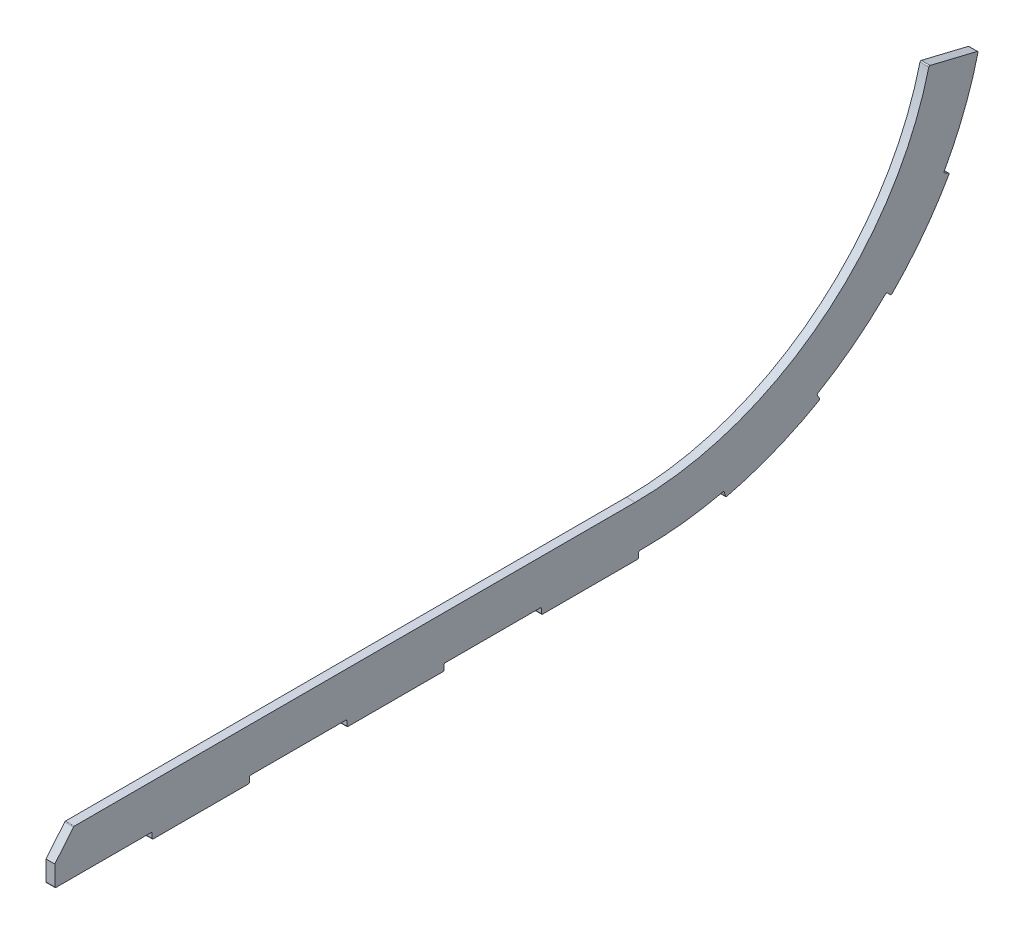
SolidWorks part; units mm, degrees
material "MS-Grade 400"
ref_plane "Front Plane" through (0, 0, 0) normal (0, 0, 1) x (1, 0, 0)
ref_plane "Top Plane" through (0, 0, 0) normal (0, 1, 0) x (1, 0, 0)
ref_plane "Right Plane" through (0, 0, 0) normal (1, 0, 0) x (0, 0, -1)
sketch "Sketch1" plane through (0, 0, 0) normal (1, 0, 0) x (0, 0, -1)
  line L0 (531, -15) -> (442.5, -15)
  line L1 (535.8793, -9) -> (531, -9)
  line L2 (0, 10) -> (17.3111, 31)
  line L3 (88.5, -9) -> (88.5, -15)
  line L4 (527.7481, 31) -> (17.3111, 31)
  line L5 (177, -9) -> (177, -15)
  line L6 (265.5, -9) -> (265.5, -15)
  line L7 (354, -9) -> (354, -15)
  line L8 (442.5, -9) -> (442.5, -15)
  line L9 (527.7481, 306) -> (610.0536, -6.2428) construction
  line L10 (535.8793, 303.5117) -> (695.9383, 28.1378) construction
  line L11 (527.7481, 306) -> (813.5032, 147.3879) construction
  line L12 (527.7481, 306) -> (760.5602, 77.7504) construction
  line L13 (535.8793, 303.5117) -> (535.8793, -9) construction
  line L14 (527.7481, 306) -> (839.704, 230.3395) construction
  line L15 (795, 241.1818) -> (839.704, 230.3395)
  line L16 (535.8793, -15) -> (0, -15) construction
  line L17 (88.5, -9) -> (0, -9)
  line L19 (0, 10) -> (0, -9)
  line L20 (535.8793, -9) -> (0, -9) construction
  line L21 (177, -15) -> (88.5, -15)
  line L22 (265.5, -9) -> (177, -9)
  line L23 (354, -15) -> (265.5, -15)
  line L24 (610.0536, -6.2428) -> (608.5239, -0.4395)
  line L25 (695.9383, 28.1378) -> (692.9232, 33.3251)
  line L26 (760.5602, 77.7504) -> (756.2755, 81.9511)
  line L27 (813.5032, 147.3879) -> (808.2572, 150.2998)
  line L28 (531, -9) -> (531, -15)
  line L29 (442.5, -9) -> (354, -9)
  arc A0 (535.8793, -9) -> (608.5239, -0.4395) centre (535.8793, 303.5117) ccw
  arc A2 (535.8793, -9) -> (839.0432, 227.6483) centre (535.8793, 303.5117) ccw construction
  arc A3 (535.8793, -15) -> (844.8637, 226.1917) centre (535.8793, 303.5117) ccw construction
  arc A4 (527.7481, 31) -> (795, 241.1818) centre (527.7481, 306) ccw
  arc A5 (610.0536, -6.2428) -> (695.9383, 28.1378) centre (535.8793, 303.5117) ccw
  arc A6 (808.2572, 150.2998) -> (839.704, 230.3395) centre (535.8793, 303.5117) ccw
  arc A7 (760.5602, 77.7504) -> (813.5032, 147.3879) centre (535.8793, 303.5117) ccw
  arc A8 (692.9232, 33.3251) -> (756.2755, 81.9511) centre (535.8793, 303.5117) ccw
  dimension "D10" = 88.5
  dimension "D11" = 88.5
  dimension "D9" = 88.5
  dimension "D21" = 340
  dimension "D7" = 6
  dimension "D8" = 15.4
  dimension "D24" = 6
  dimension "D3" = 10
  dimension "D4" = 46
  dimension "D5" = 50.5
  dimension "D6" = 13.633
  dimension "D12" = 88.5
  dimension "D13" = 88.5
  dimension "D14" = 88.5
  dimension "D15" = 795
  dimension "D16" = 15.4
  dimension "D17" = 15.4
  dimension "D18" = 19
  dimension "D19" = 15.4
  dimension "D20" = 4.8793
  dimension "D22" = 46
  dimension "D23" = 14.767
sheet metal parameters "Sheet-Metal1" thickness 8 parameters "D1"=92
base flange "Base-Flange1" sketch "Sketch1" thickness 8 reverse thickness direction no parameters "D1"=92
fillet "Fillet-1.0" radius 1 24 edges at (-4, 241.1818, -795) (-4, 230.3395, -839.704) (-4, 150.2998, -808.2572) (-4, 147.3879, -813.5032) (-4, 77.7504, -760.5602) (-4, 81.9511, -756.2755) (-4, 33.3251, -692.9232) (-4, 28.1378, -695.9383) (-4, -6.2428, -610.0536) (-4, -0.4395, -608.5239) (-4, -9, -531) (-4, -15, -531) (-4, -15, -442.5) (-4, -9, -442.5) (-4, -9, -354) (-4, -15, -354) (-4, -15, -265.5) (-4, -9, -265.5) (-4, -9, -177) (-4, -15, -177) (-4, -15, -88.5) (-4, -9, -88.5) (-4, -9, 0) (-4, 31, -17.3111)
flat pattern "Flat-Pattern1" [suppressed]
sketch "Bend-Lines1" plane through (0, 0, 0) normal (0, 1, 0) x (1, 0, 0)
sketch3d "Bounding-Box1" [suppressed]
  line L0 (-495.0122, -463.7234, 0) -> (347.8143, -235.9373, 0) construction
  line L1 (-544.7757, -279.5946, 0) -> (298.0508, -51.8085, 0) construction
  line L2 (-495.0122, -463.7234, 0) -> (-544.7757, -279.5946, 0) construction
  line L3 (347.8143, -235.9373, 0) -> (298.0508, -51.8085, 0) construction
